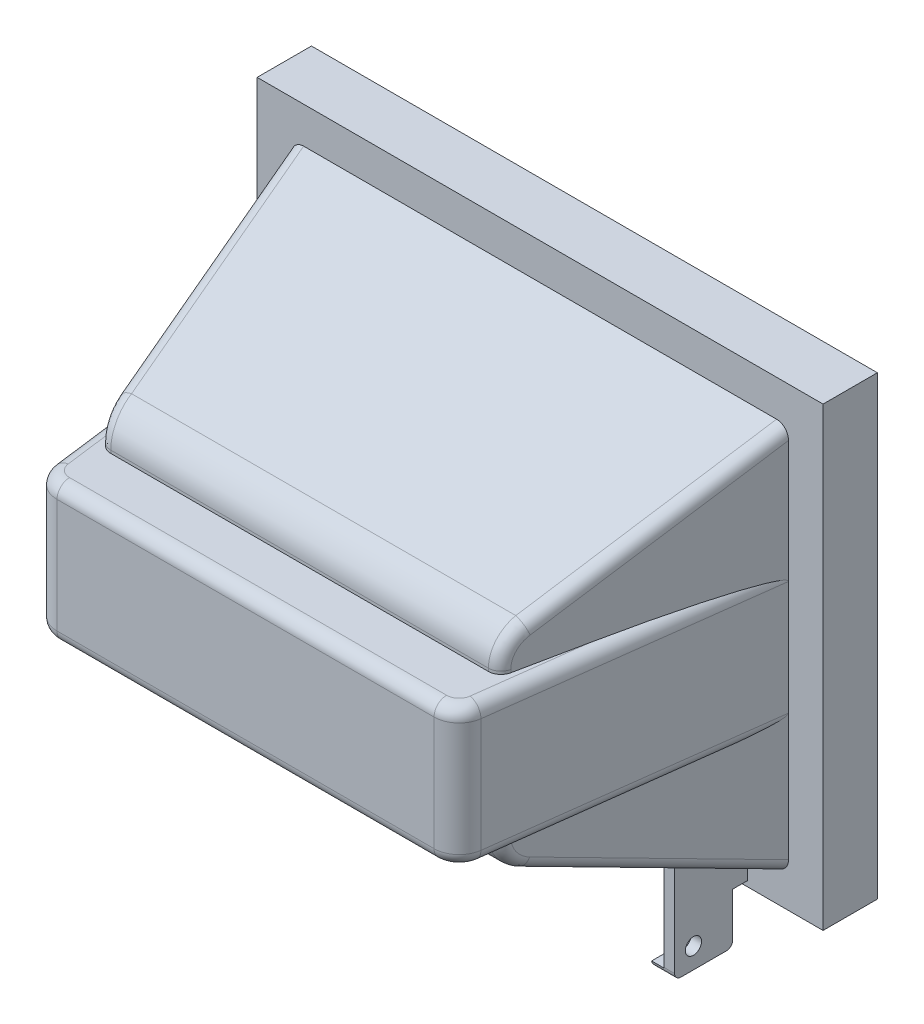
SolidWorks part; units mm, degrees
ref_plane "Front Plane" through (0, 0, 0) normal (0, 0, 1) x (1, 0, 0)
ref_plane "Top Plane" through (0, 0, 0) normal (0, 1, 0) x (1, 0, 0)
ref_plane "Right Plane" through (0, 0, 0) normal (1, 0, 0) x (0, 0, -1)
sketch "Sketch1" plane through (0, 0, 0) normal (0, 1, 0) x (1, 0, 0)
  line L1 (-90, 50.202) -> (90, 50.202)
  line L2 (-90, 50.202) -> (-90, -59.798)
  line L3 (-90, -59.798) -> (90, -59.798)
  line L4 (90, 50.202) -> (90, -59.798)
  dimension "D1" = 180
  dimension "D2" = 110
  dimension "D3" = 90
extrude "Boss-Extrude1" add sketch "Sketch1" along normal mid plane 145
sketch "Sketch4" plane through (0, 0, 0) normal (0, 1, 0) x (1, 0, 0)
  line L0 (-90, 32.932) -> (-79, 32.932)
  line L1 (-90, 50.202) -> (-90, -59.798) construction
  line L2 (-79, 32.932) -> (-60, -59.798)
  line L3 (-90, -59.798) -> (90, -59.798) construction
  line L4 (-60, -59.798) -> (-90, -59.798)
  line L5 (-90, -59.798) -> (-90, 32.932)
  line L6 (-60, -59.798) -> (60, -59.798)
  line L7 (60, -59.798) -> (79, 32.932)
  line L8 (79, 32.932) -> (90, 32.932)
  line L9 (90, -59.798) -> (90, 50.202) construction
  line L10 (90, 32.932) -> (90, -59.798)
  line L11 (90, -59.798) -> (60, -59.798)
  line L12 (90, 50.202) -> (-90, 50.202) construction
  dimension "D1" = 120
  dimension "D2" = 11
  dimension "D3" = 60
  dimension "D4" = 17.27
  dimension "D5" = 17.27
  dimension "D6" = 11
extrude "Cut-Extrude3" cut sketch "Sketch4" against normal through all and the other way through all contours L5 L4 L2 L0 | L11 L10 L8 L7
sketch "Sketch5" plane through (90, 0, 0) normal (1, 0, 0) x (0, 0, -1)
  line L0 (32.932, 60.94) -> (-43.568, 31.25)
  line L1 (32.932, -72.5) -> (32.932, 72.5) construction
  line L2 (-43.568, 31.25) -> (-43.568, -31.25)
  line L3 (-43.568, -31.25) -> (32.932, -62.5)
  line L4 (32.932, -72.5) -> (32.932, 72.5) construction
  line L5 (-59.798, 72.5) -> (32.932, 72.5) construction
  line L6 (-59.798, -72.5) -> (32.932, -72.5) construction
  line L7 (32.932, 60.94) -> (32.932, 72.5)
  line L8 (32.932, 72.5) -> (-59.798, 72.5)
  line L9 (-59.798, 72.5) -> (-59.798, -72.5)
  line L10 (-59.798, -72.5) -> (32.932, -72.5)
  line L11 (32.932, -72.5) -> (32.932, -62.5)
  dimension "D1" = 76.5
  dimension "D2" = 11.56
  dimension "D3" = 10
  dimension "D4" = 62.5
  dimension "D5" = 31.25
extrude "Cut-Extrude4" cut sketch "Sketch5" against normal through all
sketch "Sketch6" plane through (0, 0, 0) normal (0, 1, 0) x (1, 0, 0)
  line L0 (-79, 32.932) -> (-67, -60.768)
  line L1 (-67, -60.768) -> (67, -60.768)
  line L2 (67, -60.768) -> (79, 32.932)
  line L4 (-79, 32.932) -> (-63.3255, -43.568)
  line L6 (79, 32.932) -> (-79, 32.932)
  line L7 (-63.3255, -43.568) -> (63.3255, -43.568) construction
  line L8 (-63.3255, -43.568) -> (63.3255, -43.568)
  line L9 (63.3255, -43.568) -> (79, 32.932)
  dimension "D1" = 17.2
  dimension "D2" = 134
  dimension "D3" = 67
extrude "Boss-Extrude2" add sketch "Sketch6" along normal mid plane 44.25 contours L9 L8 L4 L0 L1 L2
fillet "Fillet1" radius 8 2 edges at (67, 0, 60.768) (-67, 0, 60.768)
fillet "Fillet2" radius 12 2 edges at (0, -31.25, 43.568) (0, 31.25, 43.568)
fillet "Fillet3" radius 4 22 edges at (-63.3255, -22.6572, 43.568) (-63.7432, -29.8806, 41.5293) (63.3255, -22.6572, 43.568) (63.7432, -29.8806, 41.5293) (-73.4472, -22.125, 10.4261) (-65.2446, -22.125, 58.7734) (73.4472, -22.125, 10.4261) (65.2446, -22.125, 58.7734) (73.4472, 22.125, 10.4261) (65.2446, 22.125, 58.7734) (0, 22.125, 60.768) (-65.2446, 22.125, 58.7734) (63.3255, 22.5801, 43.568) (63.7553, 29.8138, 41.47) (-63.3255, 22.5801, 43.568) (-63.7553, 29.8138, 41.47) (-71.9272, -48.3991, 1.587) (71.9272, -48.3991, 1.587) (0, -22.125, 60.768) (-73.4472, 22.125, 10.4261) (71.9473, 47.5811, 1.4889) (-71.9473, 47.5811, 1.4889)
ref_plane "Plane1" through (0, -62.5, 0) normal (0, 1, 0) x (1, 0, 0)
sketch "Sketch7" plane through (0, -62.5, 0) normal (0, 1, 0) x (1, 0, 0)
  line L0 (-75.2268, 32.932) -> (75.2268, 32.932) construction
  line L1 (-66, 32.932) -> (-58.67, 32.932)
  line L2 (-66, 32.932) -> (-66, 9.722)
  line L3 (-66, 9.722) -> (-58.67, 9.722)
  line L4 (-58.67, 32.932) -> (-58.67, 9.722)
  line L5 (-90, 50.202) -> (-90, 32.932) construction
  dimension "D1" = 23.21
  dimension "D2" = 7.33
  dimension "D3" = 24
extrude "Boss-Extrude3" add sketch "Sketch7" against normal blind 24.25 and the other way up to surface other way up to face at (0, -48.3991, 1.587)
sketch "Sketch8" plane through (0, -86.75, 0) normal (0, -1, 0) x (1, 0, 0)
  line L0 (-58.67, -9.722) -> (-58.67, -32.932) construction
  line L1 (-66, -32.932) -> (-58.67, -32.932)
  line L2 (-66, -32.932) -> (-66, -28.202)
  line L3 (-66, -28.202) -> (-58.67, -28.202)
  line L4 (-58.67, -32.932) -> (-58.67, -28.202)
  dimension "D1" = 4.73
extrude "Cut-Extrude5" cut sketch "Sketch8" against normal blind 16
sketch "Sketch9" plane through (-58.67, 0, 0) normal (1, 0, 0) x (0, 0, -1)
  line L0 (28.202, -70.75) -> (28.202, -86.75) construction
  circle A0 centre (15.702, -80.151) radius 2.575
  dimension "D2" = 5.15
  dimension "D1" = 12.5
extrude "Cut-Extrude6" cut sketch "Sketch9" against normal through all
sketch "Sketch10" plane through (-58.67, 0, 0) normal (1, 0, 0) x (0, 0, -1)
  line L0 (9.722, -84.95) -> (26.402, -84.95)
  line L1 (9.722, -53.0188) -> (9.722, -86.75) construction
  line L2 (26.402, -84.95) -> (26.402, -68.95)
  line L3 (26.402, -68.95) -> (31.132, -68.95)
  line L4 (31.132, -68.95) -> (31.132, -62.5)
  line L5 (61.0335, -62.5) -> (-61.0335, -62.5) construction
  line L6 (9.722, -86.75) -> (28.202, -86.75) construction
  line L7 (28.202, -70.75) -> (28.202, -86.75) construction
  line L8 (32.932, -70.75) -> (28.202, -70.75) construction
  line L9 (32.932, -70.75) -> (32.932, -62.5) construction
  line L10 (31.132, -62.5) -> (31.3894, -61.8699)
  line L11 (9.722, -53.0188) -> (32.932, -62.5) construction
  line L12 (31.3894, -61.8699) -> (9.722, -53.0188)
  line L13 (9.722, -53.0188) -> (9.722, -84.95)
  dimension "D1" = 1.8
  dimension "D2" = 1.8
  dimension "D3" = 1.8
  dimension "D4" = 1.8
extrude "Cut-Extrude7" cut sketch "Sketch10" against normal blind 4
fillet "Fillet4" radius 2 1 edges at (-62.335, -86.75, -28.202)
fillet "Fillet5" radius 1 1 edges at (-60.67, -84.95, -26.402)
fillet "Fillet6" radius 2 1 edges at (-62.335, -86.75, -9.722)
mirror "Mirror1" about plane through (0, 0, 0) normal (1, 0, 0) of "Boss-Extrude3", "Cut-Extrude5", "Cut-Extrude6", "Cut-Extrude7", "Fillet5", "Fillet4", "Fillet6"
sketch "Sketch11" plane through (0, 0, -50.202) normal (0, 0, -1) x (-1, 0, 0)
  line L1 (-70.5036, 52.9118) -> (70.5036, 52.9118)
  line L2 (-70.5036, 52.9118) -> (-70.5036, -52.9118)
  line L3 (-70.5036, -52.9118) -> (70.5036, -52.9118)
  line L4 (70.5036, 52.9118) -> (70.5036, -52.9118)
  line L5 (-70.5036, 52.9118) -> (70.5036, -52.9118) construction
  line L6 (-70.5036, -52.9118) -> (70.5036, 52.9118) construction
  point P0 (0, 0)
extrude "Cut-Extrude8" cut sketch "Sketch11" against normal blind 70 draft 15
sketch "Sketch12" plane through (-73.5757, 0, 9.4227) normal (-0.9919, 0, 0.127) x (0.127, 0, 0.9919)
  circle A0 centre (0, 0) radius 5
extrude "Boss-Extrude4" add sketch "Sketch12" against normal blind 140
